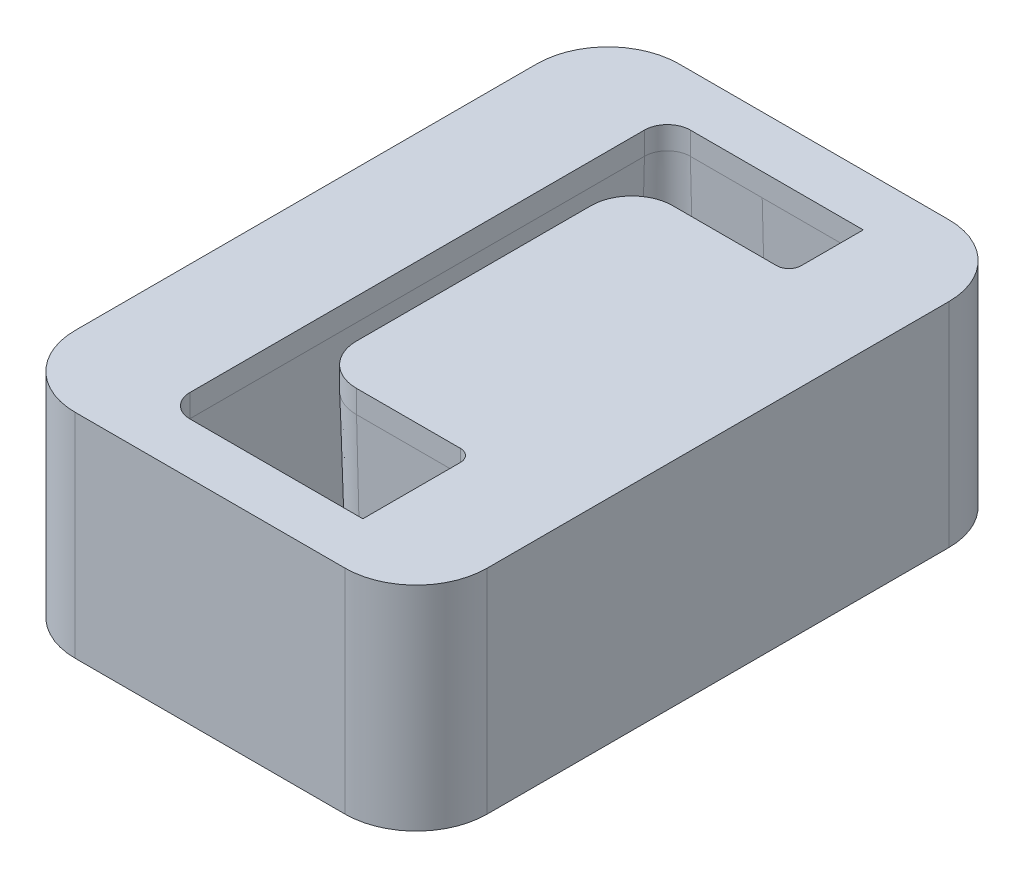
SolidWorks part; units mm, degrees
material "K110"
ref_plane "Front Plane" through (0, 0, 0) normal (0, 0, 1) x (1, 0, 0)
ref_plane "Top Plane" through (0, 0, 0) normal (0, 1, 0) x (1, 0, 0)
ref_plane "Right Plane" through (0, 0, 0) normal (1, 0, 0) x (0, 0, -1)
sketch "Sketch1" plane through (0, 0, 0) normal (0, 1, 0) x (1, 0, 0)
  line L1 (-29, -42.5) -> (29, -42.5)
  line L2 (-29, -42.5) -> (-29, 42.5)
  line L3 (-29, 42.5) -> (29, 42.5)
  line L4 (29, -42.5) -> (29, 42.5)
  line L5 (-29, -42.5) -> (29, 42.5) construction
  line L6 (-29, 42.5) -> (29, -42.5) construction
  point P0 (0, 0)
  dimension "D1" = 85
  dimension "D2" = 58
extrude "Boss-Extrude1" add sketch "Sketch1" against normal blind 30
fillet "Fillet1" radius 10 4 edges at (-29, -15, -42.5) (29, -15, -42.5) (29, -15, 42.5) (-29, -15, 42.5)
sketch "Sketch2" plane through (0, 0, 0) normal (0, 1, 0) x (1, 0, 0)
  line L16 (14.23, 35.23) -> (-10.12, 35.23)
  line L17 (-13.35, 32) -> (-13.35, -32)
  line L18 (-10.12, -35.23) -> (14.23, -35.23)
  line L19 (14.23, -35.23) -> (14.23, -21.5)
  line L20 (12.5, -19.77) -> (-2.12, -19.77)
  line L21 (-7.89, -14) -> (-7.89, 19)
  line L22 (-2.12, 24.77) -> (12.5, 24.77)
  line L23 (14.23, 26.5) -> (14.23, 35.23)
  line L24 (14.23, 35.23) -> (-10.12, 35.23)
  line L25 (-13.35, 32) -> (-13.35, -32)
  line L26 (-10.12, -35.23) -> (14.23, -35.23)
  line L27 (14.23, -35.23) -> (14.23, -21.5)
  line L28 (12.5, -19.77) -> (-2.12, -19.77)
  line L29 (-7.89, -14) -> (-7.89, 19)
  line L30 (-2.12, 24.77) -> (12.5, 24.77)
  line L31 (14.23, 26.5) -> (14.23, 35.23)
  arc A12 (-10.12, 35.23) -> (-13.35, 32) centre (-10.12, 32) ccw
  arc A13 (-13.35, -32) -> (-10.12, -35.23) centre (-10.12, -32) ccw
  arc A14 (14.23, -21.5) -> (12.5, -19.77) centre (12.5, -21.5) ccw
  arc A15 (-7.89, -14) -> (-2.12, -19.77) centre (-2.12, -14) ccw
  arc A16 (-2.12, 24.77) -> (-7.89, 19) centre (-2.12, 19) ccw
  arc A17 (12.5, 24.77) -> (14.23, 26.5) centre (12.5, 26.5) ccw
  arc A18 (-10.12, 35.23) -> (-13.35, 32) centre (-10.12, 32) ccw
  arc A19 (-13.35, -32) -> (-10.12, -35.23) centre (-10.12, -32) ccw
  arc A20 (14.23, -21.5) -> (12.5, -19.77) centre (12.5, -21.5) ccw
  arc A21 (-7.89, -14) -> (-2.12, -19.77) centre (-2.12, -14) ccw
  arc A22 (-2.12, 24.77) -> (-7.89, 19) centre (-2.12, 19) ccw
  arc A23 (12.5, 24.77) -> (14.23, 26.5) centre (12.5, 26.5) ccw
  dimension "D1" = 0.23
extrude "Cut-Extrude1" cut sketch "Sketch2" against normal up to next
sketch "Sketch3" plane through (0, 0, 0) normal (1, 0, 0) x (0, 0, -1)
  line L0 (35.23, -3.2) -> (35.9318, -30)
  line L1 (35.23, -30) -> (35.23, 0) construction
  line L2 (32.5, -30) -> (42.5, -30) construction
  line L3 (35.9318, -30) -> (35.23, -30)
  line L4 (35.23, -30) -> (35.23, -3.2)
  line L5 (31.9, 0) -> (-31.9, 0) construction
  dimension "D1" = 3.2
  dimension "D2" = 1.5
sketch "Sketch5" plane through (0, 0, 0) normal (0, 1, 0) x (1, 0, 0)
  line L0 (12.5, -19.77) -> (-2.12, -19.77) construction
  line L1 (14.23, -35.23) -> (14.23, -21.5) construction
  line L2 (-10.12, -35.23) -> (14.23, -35.23) construction
  line L3 (-7.89, -14) -> (-7.89, 19) construction
  line L4 (-2.12, 24.77) -> (12.5, 24.77) construction
  line L5 (-13.35, 32) -> (-13.35, -32) construction
  line L6 (14.23, 35.23) -> (-10.12, 35.23) construction
  line L7 (14.23, 26.5) -> (14.23, 35.23) construction
  line L8 (12.5, -19.77) -> (-2.12, -19.77)
  line L9 (14.23, -35.23) -> (14.23, -21.5)
  line L10 (-10.12, -35.23) -> (14.23, -35.23)
  line L11 (-7.89, -14) -> (-7.89, 19)
  line L12 (-2.12, 24.77) -> (12.5, 24.77)
  line L13 (-13.35, 32) -> (-13.35, -32)
  line L14 (14.23, 35.23) -> (-10.12, 35.23)
  line L15 (14.23, 26.5) -> (14.23, 35.23)
  arc A0 (-7.89, -14) -> (-2.12, -19.77) centre (-2.12, -14) ccw construction
  arc A1 (14.23, -21.5) -> (12.5, -19.77) centre (12.5, -21.5) ccw construction
  arc A2 (-13.35, -32) -> (-10.12, -35.23) centre (-10.12, -32) ccw construction
  arc A3 (-2.12, 24.77) -> (-7.89, 19) centre (-2.12, 19) ccw construction
  arc A4 (-10.12, 35.23) -> (-13.35, 32) centre (-10.12, 32) ccw construction
  arc A5 (12.5, 24.77) -> (14.23, 26.5) centre (12.5, 26.5) ccw construction
  arc A6 (-7.89, -14) -> (-2.12, -19.77) centre (-2.12, -14) ccw
  arc A7 (14.23, -21.5) -> (12.5, -19.77) centre (12.5, -21.5) ccw
  arc A8 (-13.35, -32) -> (-10.12, -35.23) centre (-10.12, -32) ccw
  arc A9 (-2.12, 24.77) -> (-7.89, 19) centre (-2.12, 19) ccw
  arc A10 (-10.12, 35.23) -> (-13.35, 32) centre (-10.12, 32) ccw
  arc A11 (12.5, 24.77) -> (14.23, 26.5) centre (12.5, 26.5) ccw
sweep "Cut-Sweep1" cut profiles "Sketch3" path "Sketch5"
hole_wizard "M6 Tapped Hole1" positions "Sketch8" profile "Sketch7" tap size "M6" standard "ISO"
sketch "Sketch8" plane through (0, -30, 0) normal (0, -1, 0) x (-1, 0, 0)
  line L0 (-19, 42.5) -> (19, 42.5) construction
  line L1 (-29, -32.5) -> (-29, 32.5) construction
  line L2 (29, 32.5) -> (29, -32.5) construction
  line L3 (19, -42.5) -> (-19, -42.5) construction
  point P0 (-22, 35.5)
  point P2 (22, 35.5)
  point P4 (22, -35.5)
  point P6 (-22, -35.5)
  dimension "D1" = 7
  dimension "D2" = 7
  dimension "D3" = 7
  dimension "D4" = 7
sketch "Sketch7" plane through (22, -30, -35.5) normal (1, 0, 0) x (0, 0, -1)
  line L0 (0, 0) -> (0, 18.5022)
  line L1 (0, 18.5022) -> (2.5, 17)
  line L2 (2.5, 17) -> (2.5, 0.525)
  line L3 (2.5, 0.525) -> (3.025, 0)
  line L5 (3.025, 0) -> (0, 0)
  line L6 (-2.5, 0.525) -> (-3.025, 0) construction
  line L10 (0, 18.5022) -> (-2.5, 17) construction
  line L11 (0, -6.35) -> (0, 107.95) construction
  dimension "Tap Drill Dia." = 5
  dimension "Tap Drill Depth" = 17
  dimension "Near C'Sink Dia." = 6.05
  dimension "Near C'Sink Angle" = 90
  dimension "Drill Angle" = 118
cosmetic thread "Hole Thread1"
cosmetic thread "Hole Thread2"
cosmetic thread "Hole Thread3"
cosmetic thread "Hole Thread4"
